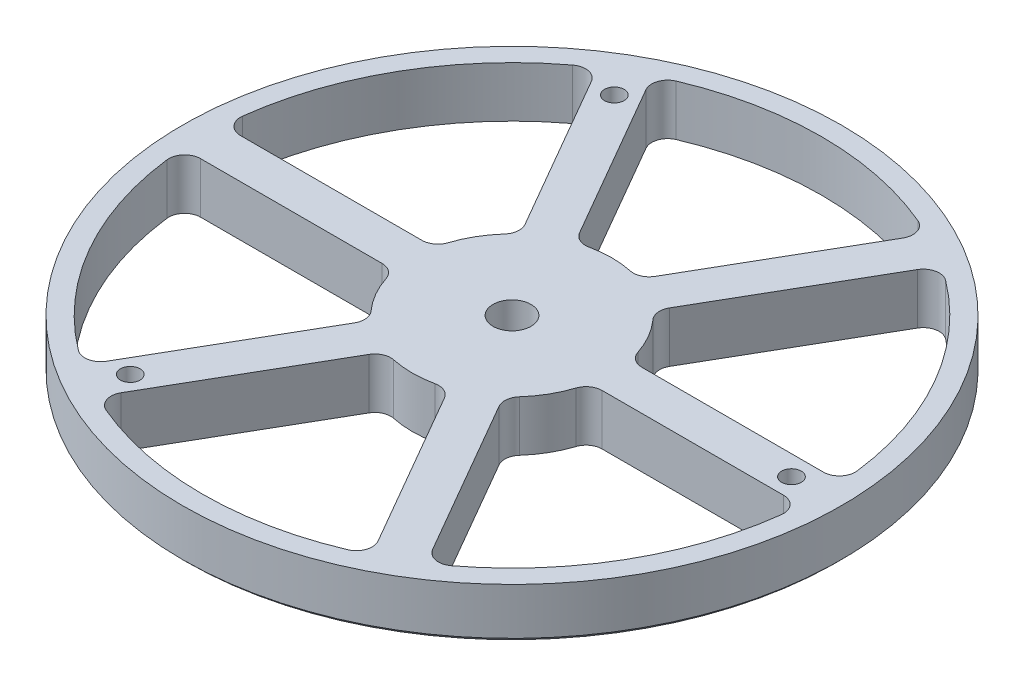
SolidWorks part; units mm, degrees
material "6061-T6 (SS)"
ref_plane "Front Plane" through (0, 0, 0) normal (0, 0, 1) x (1, 0, 0)
ref_plane "Top Plane" through (0, 0, 0) normal (0, 1, 0) x (1, 0, 0)
ref_plane "Right Plane" through (0, 0, 0) normal (1, 0, 0) x (0, 0, -1)
sketch "Sketch2" plane through (0, 0, 0) normal (1, 0, 0) x (0, 0, -1)
  line L0 (0, 0) -> (-82.55, 0)
  line L1 (-82.55, 0) -> (-82.55, 12.7)
  line L2 (-82.55, 12.7) -> (0, 12.7)
  line L5 (0, 12.7) -> (0, 0)
  dimension "D1" = 82.55
  dimension "D2" = 12.7
ref_axis "Axis1" through (0, -0.635, 0) along (0, 1, 0)
revolve "Revolve1" add sketch "Sketch2" angle 360 about axis through (0, -0.635, 0) along (0, 1, 0)
hole_wizard "#10 (0.1935) Diameter Hole1" positions "Sketch6" profile "Sketch7" hole size "#10" standard "ANSI Inch" end condition through all
sketch "Sketch6" plane through (0, 12.7, 0) normal (0, 1, 0) x (1, 0, 0)
  line L0 (0, 0) -> (-69.8201, 120.932) construction
  line L2 (0, 0) -> (0, 109.0908) construction
  point P0 (-35, 60.6218)
  dimension "D1" = 30
  dimension "D2" = 70
sketch "Sketch7" plane through (-35, 12.7, -60.6218) normal (1, 0, 0) x (0, 0, 1)
  line L0 (0, 0) -> (0, 12.7)
  line L1 (0, 12.7) -> (2.4574, 12.7)
  line L2 (2.4574, 12.7) -> (2.4574, 0)
  line L5 (2.4574, 0) -> (0, 0)
  line L11 (0, -6.35) -> (0, 107.95) construction
  dimension "Thru Hole Dia." = 4.9149
  dimension "Thru Hole Depth" = 12.7
pattern_circular "CirPattern3" count 3 over 360 about axis through (0, -0.635, 0) along (0, 1, 0) of "#10 (0.1935) Diameter Hole1"
sketch "Sketch8" plane through (0, 12.7, 0) normal (0, 1, 0) x (1, 0, 0)
  line L4 (0, 0) -> (0, 93.9995) construction
  line L5 (0, 0) -> (113.8372, 0) construction
  line L6 (-7.9173, 23.7132) -> (-34.3642, 69.5205)
  line L7 (7.9173, 23.7132) -> (34.3642, 69.5205)
  line L8 (0, 0) -> (-35, 60.6218) construction
  arc A0 (-7.9173, 23.7132) -> (7.9173, 23.7132) centre (0, 0) cw
  arc A1 (-34.3642, 69.5205) -> (34.3642, 69.5205) centre (0, 0) cw
  circle A2 centre (0, 0) radius 82.55 construction
  dimension "D1" = 25
  dimension "D2" = 5
  dimension "D3" = 5
extrude "Cut-Extrude1" cut sketch "Sketch8" against normal through all
fillet "Fillet1" radius 4 4 edges at (7.9173, 6.35, -23.7132) (34.3642, 6.35, -69.5205) (-7.9173, 6.35, -23.7132) (-34.3642, 6.35, -69.5205)
pattern_circular "CirPattern4" count 6 over 360 about axis through (0, -0.635, 0) along (0, 1, 0) of "Cut-Extrude1", "Fillet1"
chamfer "Chamfer2" distance 1 angle 45 1 edges at (0, 0, -82.55)
hole_wizard "3/8 (0.375) Diameter Hole1" positions "Sketch9" profile "Sketch11" hole size "3/8" standard "ANSI Inch" end condition through all
sketch "Sketch9" plane through (0, 0, 0) normal (0, -1, 0) x (-1, 0, 0)
  point P0 (0, 0)
sketch "Sketch11" plane through (0, 0, 0) normal (1, 0, 0) x (0, 0, -1)
  line L0 (0, 0) -> (0, 12.7)
  line L1 (0, 12.7) -> (4.7625, 12.7)
  line L2 (4.7625, 12.7) -> (4.7625, 0)
  line L5 (4.7625, 0) -> (0, 0)
  line L11 (0, -6.35) -> (0, 107.95) construction
  dimension "Thru Hole Dia." = 9.525
  dimension "Thru Hole Depth" = 12.7
equation "\"TubeDiameter\" = 6.500in"
equation "\"D1@Sketch2\"=\"TubeDiameter\"/2"
